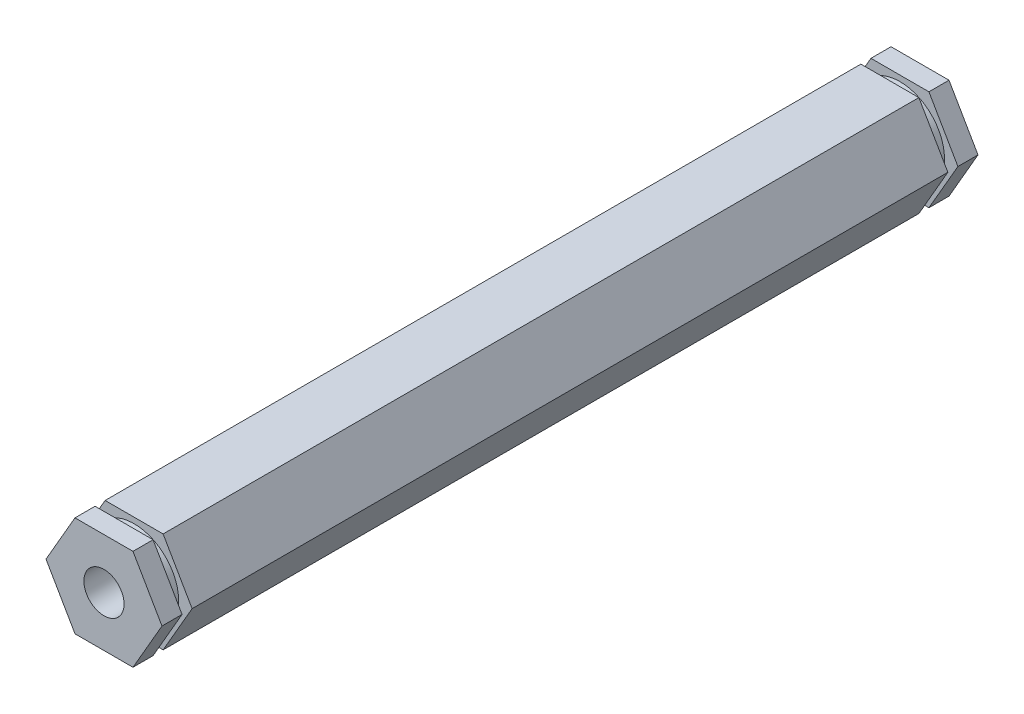
SolidWorks part; units mm, degrees
ref_plane "Front Plane" through (0, 0, 0) normal (0, 0, 1) x (1, 0, 0)
ref_plane "Top Plane" through (0, 0, 0) normal (0, 1, 0) x (1, 0, 0)
ref_plane "Right Plane" through (0, 0, 0) normal (1, 0, 0) x (0, 0, -1)
sketch "Sketch1" plane through (0, 0, 0) normal (0, 0, 1) x (1, 0, 0)
  line L1 (7.3323, 0) -> (3.6662, 6.35)
  line L2 (3.6662, 6.35) -> (-3.6662, 6.35)
  line L3 (-3.6662, 6.35) -> (-7.3323, 0)
  line L4 (-7.3323, 0) -> (-3.6662, -6.35)
  line L5 (-3.6662, -6.35) -> (3.6662, -6.35)
  line L6 (3.6662, -6.35) -> (7.3323, 0)
  circle A0 centre (0, 0) radius 6.35 construction
extrude "Boss-Extrude1" add sketch "Sketch1" along normal blind 103.1875
ref_plane "Plane1" through (0, 0, 2.54) normal (0, 0, 1) x (1, 0, 0)
sketch "Sketch2" plane through (0, 0, 2.54) normal (0, 0, 1) x (1, 0, 0)
  circle A0 centre (0, 0) radius 5.6353
  circle A1 centre (0, 0) radius 9.9097
extrude "Cut-Extrude1" cut sketch "Sketch2" along normal blind 1.27
sketch "Sketch3" plane through (0, 0, 0) normal (0, 0, -1) x (-1, 0, 0)
  circle A0 centre (0, 0) radius 2.54
  dimension "D1" = 5.08
extrude "Cut-Extrude2" cut sketch "Sketch3" against normal blind 25.4
ref_plane "Plane2" through (0, 0, 100.6475) normal (0, 0, 1) x (1, 0, 0)
sketch "Sketch4" plane through (0, 0, 100.6475) normal (0, 0, 1) x (1, 0, 0)
  circle A0 centre (0, 0) radius 5.6353 construction
  circle A1 centre (0, 0) radius 5.6353
  circle A2 centre (0, 0) radius 26.1342
extrude "Cut-Extrude3" cut sketch "Sketch4" against normal blind 1.27
sketch "Sketch5" plane through (0, 0, 103.1875) normal (0, 0, 1) x (1, 0, 0)
  circle A0 centre (0, 0) radius 2.54
  dimension "D1" = 5.08
extrude "Cut-Extrude4" cut sketch "Sketch5" against normal blind 25.4
ref_axis "Center_Axis" through (0, 0, -34.7023) along (0, 0, 1)
